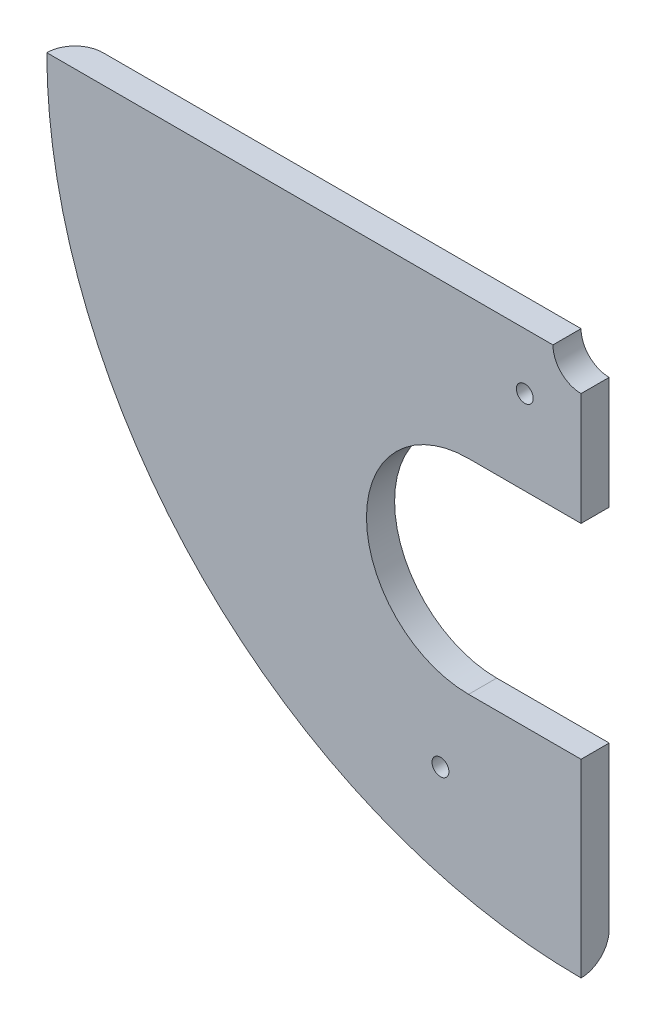
SolidWorks part; units mm, degrees
ref_plane "前基準面" through (0, 0, 0) normal (0, 0, 1) x (1, 0, 0)
ref_plane "上基準面" through (0, 0, 0) normal (0, 1, 0) x (1, 0, 0)
ref_plane "右基準面" through (0, 0, 0) normal (1, 0, 0) x (0, 0, -1)
sketch "草圖1" plane through (0, 0, 0) normal (0, 0, 1) x (1, 0, 0)
  line L0 (-95, 0) -> (-5, 0) construction
  line L1 (-5, 0) -> (-95, 0)
  line L2 (0, -5) -> (0, -95)
  line L3 (95, 0) -> (168.4046, 0) construction
  arc A0 (-95, 0) -> (0, -95) centre (0, 0) ccw
  circle A1 centre (-10, -10) radius 1.5
  arc A3 (-5, 0) -> (0, -5) centre (0, 0) ccw
  circle A4 centre (-25, -75) radius 1.5
  point P16 (0, 0)
  dimension "D1" = 190
  dimension "D2" = 3
  dimension "D9" = 5
  dimension "D4" = 10
  dimension "D8" = 10
extrude "填料-伸長1" add sketch "草圖1" along normal blind 5 contours A1 | A4 | A0 L2 A3 L1 region at (-10, -10, 0) region at (-25, -75, 0)
sketch "草圖2" plane through (0, 0, 0) normal (0, 0, -1) x (-1, 0, 0)
  line L0 (0, -25) -> (0, -61.3121)
  line L3 (-107.2857, 0) -> (167.8844, 0) construction
  line L4 (20, -43.156) -> (0, -43.156) construction
  line L5 (20, -61.3121) -> (0, -61.3121)
  line L6 (20, -25) -> (0, -25)
  arc A2 (20, -61.3121) -> (20, -25) centre (20, -43.156) ccw
  point P2 (0, 35)
  point P15 (0, -35)
  point P20 (0, 0)
  dimension "D1" = 25
extrude "除料-伸長1" cut sketch "草圖2" against normal through all
fillet "圓角2" radius 5 1 edges at (-67.1751, -67.1751, 0)
